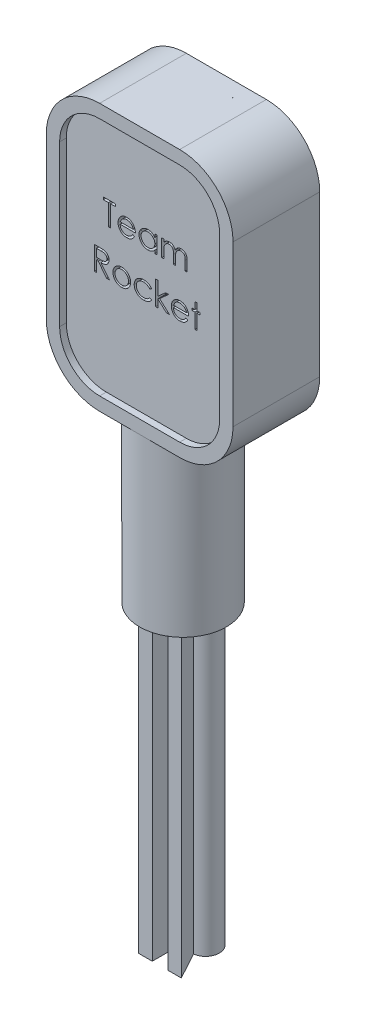
SolidWorks part; units mm, degrees
ref_plane "Front Plane" through (0, 0, 0) normal (0, 0, 1) x (1, 0, 0)
ref_plane "Top Plane" through (0, 0, 0) normal (0, 1, 0) x (1, 0, 0)
ref_plane "Right Plane" through (0, 0, 0) normal (1, 0, 0) x (0, 0, -1)
sketch "Sketch7" plane through (0, 0, 0) normal (0, 1, 0) x (1, 0, 0)
  line L0 (-2.83, 4.28) -> (-0.55, 4.28)
  line L1 (-2.83, 4.28) -> (-2.83, 0)
  line L2 (-0.55, 4.28) -> (-0.55, 0)
  line L3 (-2.83, 0) -> (-0.55, 0)
  line L4 (0, 0) -> (-7.1941, 0) construction
  line L5 (-2.73, 4.28) -> (-2.73, -4.06)
  line L6 (-0.55, 4.28) -> (1.27, 4.28)
  line L8 (-0.55, 0) -> (1.6498, -4.06)
  line L9 (1.67, 0) -> (3.8698, -4.06)
  line L10 (1.6498, -4.06) -> (3.8698, -4.06)
  line L11 (-2.83, 0) -> (-0.55, 0)
  line L12 (-2.83, 0) -> (-2.83, -4.06)
  line L13 (-2.83, -4.06) -> (-0.55, -4.06)
  line L14 (-0.55, 0) -> (-0.55, -4.06)
  line L15 (-2.9291, -4.06) -> (3.2467, -4.06) construction
  line L16 (-0.55, 0) -> (8.5952, 0) construction
  line L18 (-2.83, -3.96) -> (-0.55, -3.96)
  line L19 (-0.5278, 0.2) -> (-0.55, 0.2)
  line L20 (-0.65, -4.06) -> (-0.65, 0)
  line L21 (-0.65, 0) -> (-0.65, 0.2099)
  line L22 (1.7636, -4.06) -> (-0.55, 0.2099)
  line L23 (1.5956, -3.96) -> (3.8156, -3.96)
  line L24 (-0.65, 0.2099) -> (-0.55, 0.2099)
  line L25 (3.7561, -4.06) -> (1.5144, 0.0772)
  line L26 (-2.83, 4.18) -> (1.27, 4.18)
  arc A0 (1.27, 4.28) -> (1.67, 0) centre (1.27, 2.1213) cw
  circle A1 centre (0, 0) radius 6.5
  arc A3 (1.27, 4.18) -> (1.5144, 0.0772) centre (1.27, 2.1213) cw
  point P11 (-0.55, 0)
  dimension "D3" = 2.22
  dimension "D9" = 0.1
  dimension "D1" = 13
  dimension "D10" = 0.1
  dimension "D11" = 0.1
  dimension "D15" = 2.0587
  dimension "D2" = 0.55
  dimension "D4" = 1.82
  dimension "D5" = 2.28
  dimension "D6" = 4.06
  dimension "D7" = 4.28
  dimension "D8" = 28.45
  dimension "D12" = 0.1
  dimension "D13" = 0.1
  dimension "D14" = 0.1
extrude "Boss-Extrude4" add sketch "Sketch7" along normal blind 45 contours L18 L20 L3 L5 | L26 L5 L3 L21 L24 L2 | A3 L26 L2 L22 L23 L25 region at (-1.6424, 0, -2.0946) region at (1.3503, 0, -0.6497) region at (-1.69, 0, 1.98)
sketch "Sketch9" plane through (0, 45, 0) normal (0, 1, 0) x (1, 0, 0)
  line L2 (0, 0) -> (0, 8.082) construction
  circle A0 centre (0, 0) radius 6.5
  point P0 (0, 0)
  point P10 (0, 0)
  point P13 (-0.6549, 0.3231)
  dimension "D3" = 13
extrude "Boss-Extrude5" add sketch "Sketch9" along normal blind 25
sketch "Sketch10" plane through (0, 70, 0) normal (0, 1, 0) x (1, 0, 0)
  line L0 (-14, -6.5) -> (-14, 6.5)
  line L1 (-14, -6.5) -> (14, -6.5)
  line L2 (-14, 6.5) -> (14, 6.5)
  line L3 (14, -6.5) -> (14, 6.5)
  line L4 (-14, -6.5) -> (14, 6.5) construction
  line L5 (-14, 6.5) -> (14, -6.5) construction
  circle A0 centre (3.2555, 4.2368) radius 0.0375
  point P1 (0, 0)
  dimension "D1" = 13
  dimension "D2" = 28
extrude "Boss-Extrude6" add sketch "Sketch10" along normal blind 40
fillet "Fillet3" radius 8 1 edges at (14, 70, 0) type face fillet first side face at (8.625, 70, 0) second side face at (14, 90, 0)
fillet "Fillet4" radius 8 1 edges at (-14, 70, 0) type face fillet first side face at (-8.625, 70, 0) second side face at (-14, 90, 0)
fillet "Fillet5" radius 8 1 edges at (14, 110, 0) type face fillet first side face at (14, 94, 0) second side face at (0, 110, 0)
fillet "Fillet6" radius 8 1 edges at (-14, 110, 0) type face fillet first side face at (-14, 94, 0) second side face at (-4, 110, 0)
sketch "Sketch11" plane through (0, 0, -6.5) normal (0, 0, -1) x (-1, 0, 0)
  line L15 (12, 78) -> (12, 102)
  line L16 (6, 108) -> (-6, 108)
  line L17 (-12, 102) -> (-12, 78)
  line L18 (-6, 72) -> (0, 72)
  line L19 (0, 72) -> (6, 72)
  line L20 (12, 78) -> (12, 102)
  line L21 (6, 108) -> (-6, 108)
  line L22 (-12, 102) -> (-12, 78)
  line L23 (-6, 72) -> (0, 72)
  line L24 (0, 72) -> (6, 72)
  arc A12 (12, 102) -> (6, 108) centre (6, 102) ccw
  arc A13 (-6, 108) -> (-12, 102) centre (-6, 102) ccw
  arc A14 (-12, 78) -> (-6, 72) centre (-6, 78) ccw
  arc A15 (6, 72) -> (12, 78) centre (6, 78) ccw
  arc A16 (12, 102) -> (6, 108) centre (6, 102) ccw
  arc A17 (-6, 108) -> (-12, 102) centre (-6, 102) ccw
  arc A18 (-12, 78) -> (-6, 72) centre (-6, 78) ccw
  arc A19 (6, 72) -> (12, 78) centre (6, 78) ccw
  dimension "D1" = 2
extrude "Cut-Extrude1" cut sketch "Sketch11" against normal blind 1 contours L20 A16 L21 A17 L22 A18 L23 L24 A19
sketch "Sketch12" plane through (0, 0, 6.5) normal (0, 0, 1) x (1, 0, 0)
  line L10 (6, 108) -> (-6, 108)
  line L11 (-12, 102) -> (-12, 78)
  line L12 (-6, 72) -> (0, 72)
  line L13 (0, 72) -> (6, 72)
  line L14 (12, 78) -> (12, 102)
  line L15 (6, 108) -> (-6, 108)
  line L16 (-12, 102) -> (-12, 78)
  line L17 (-6, 72) -> (0, 72)
  line L18 (0, 72) -> (6, 72)
  line L19 (12, 78) -> (12, 102)
  arc A8 (-6, 108) -> (-12, 102) centre (-6, 102) ccw
  arc A9 (-12, 78) -> (-6, 72) centre (-6, 78) ccw
  arc A10 (6, 72) -> (12, 78) centre (6, 78) ccw
  arc A11 (12, 102) -> (6, 108) centre (6, 102) ccw
  arc A12 (-6, 108) -> (-12, 102) centre (-6, 102) ccw
  arc A13 (-12, 78) -> (-6, 72) centre (-6, 78) ccw
  arc A14 (6, 72) -> (12, 78) centre (6, 78) ccw
  arc A15 (12, 102) -> (6, 108) centre (6, 102) ccw
  dimension "D1" = 2
extrude "Cut-Extrude2" cut sketch "Sketch12" against normal blind 1
sketch "Sketch13" plane through (0, 0, 5.5) normal (0, 0, 1) x (1, 0, 0)
  line L0 (-12, 93.6273) -> (12, 93.6273) construction
  line L1 (-12, 102) -> (-12, 78) construction
  line L2 (12, 78) -> (12, 102) construction
  text T0 "Team\r\nRocket"
extrude "Cut-Extrude3" cut sketch "Sketch13" against normal blind 1.5
